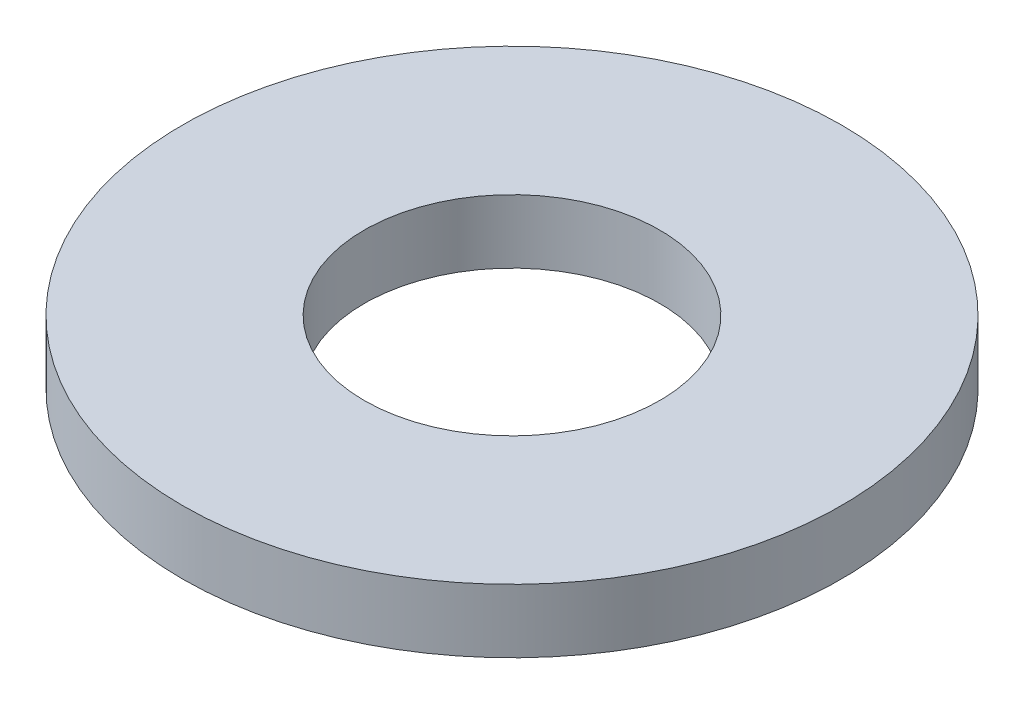
SolidWorks part; units mm, degrees
ref_plane "Front Plane" through (0, 0, 0) normal (0, 0, 1) x (1, 0, 0)
ref_plane "Top Plane" through (0, 0, 0) normal (0, 1, 0) x (1, 0, 0)
ref_plane "Right Plane" through (0, 0, 0) normal (1, 0, 0) x (0, 0, -1)
sketch "Sketch1" plane through (0, 0, 0) normal (0, 1, 0) x (1, 0, 0)
  circle A0 centre (0, 0) radius 72.5
  dimension "FLANGE_OD" = 145
extrude "Boss-Extrude1" add sketch "Sketch1" along normal blind 14
sketch "Sketch2" plane through (0, 0, 0) normal (0, 1, 0) x (1, 0, 0)
  circle A0 centre (0, 0) radius 32.5
  dimension "BORE_D" = 65
extrude "Cut-Extrude1" cut sketch "Sketch2" along normal through all
sketch "Sketch3" plane through (0, 14, 0) normal (0, 1, 0) x (1, 0, 0)
  circle A0 centre (0, 0) radius 25.6442 construction
  circle A1 centre (-25.6442, 0) radius 2.8693
  dimension "BOLT_D" = 5.7386
  dimension "BOLT_PCD" = 51.2884
extrude "Cut-Extrude2" cut sketch "Sketch3" against normal blind 11.0702 rebuild error yes
pattern_circular "CirPattern1" count 4 over 360 rebuild error yes
